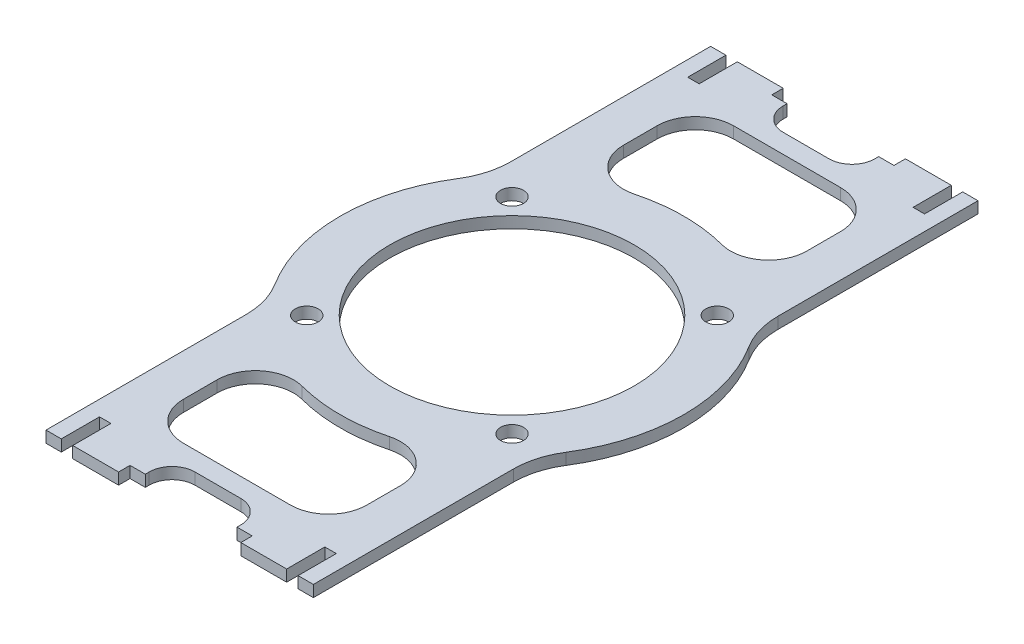
SolidWorks part; units mm, degrees
material "1023 Arkusz stali węglowej (SS)"
ref_plane "Płaszczyzna przednia" through (0, 0, 0) normal (0, 0, 1) x (1, 0, 0)
ref_plane "Płaszczyzna górna" through (0, 0, 0) normal (0, 1, 0) x (1, 0, 0)
ref_plane "Płaszczyzna prawa" through (0, 0, 0) normal (1, 0, 0) x (0, 0, -1)
sketch "Szkic1" plane through (0, 0, 0) normal (0, 1, 0) x (1, 0, 0)
  line L166 (594.7127, -59.8621) -> (606.7127, -59.8621)
  line L167 (606.7127, -59.8621) -> (606.7127, -56.8621)
  line L168 (591.7127, -49.8621) -> (591.7127, -59.8621)
  line L169 (591.7127, -59.8621) -> (587.7127, -59.8621)
  line L170 (610.7127, -56.8621) -> (610.7127, -55.8621)
  line L171 (616.7127, -49.8621) -> (622.7127, -49.8621)
  line L172 (606.7127, -56.8621) -> (610.7127, -56.8621)
  line L173 (587.7127, -59.8621) -> (587.7127, -7.5032)
  line L174 (608.7127, -44.8621) -> (622.7127, -44.8621)
  line L175 (598.7127, -26.0505) -> (598.7127, -34.8621)
  line L176 (594.7127, -59.8621) -> (594.7127, -49.8621)
  line L177 (591.7127, -49.8621) -> (594.7127, -49.8621)
  line L178 (594.7127, 114.1379) -> (606.7127, 114.1379)
  line L179 (606.7127, 114.1379) -> (606.7127, 111.1379)
  line L180 (591.7127, 104.1379) -> (591.7127, 114.1379)
  line L181 (591.7127, 114.1379) -> (587.7127, 114.1379)
  line L182 (610.7127, 111.1379) -> (610.7127, 110.1379)
  line L183 (616.7127, 104.1379) -> (622.7127, 104.1379)
  line L184 (606.7127, 111.1379) -> (610.7127, 111.1379)
  line L185 (587.7127, 114.1379) -> (587.7127, 61.7789)
  line L186 (608.7127, 99.1379) -> (622.7127, 99.1379)
  line L187 (598.7127, 80.3262) -> (598.7127, 89.1379)
  line L188 (594.7127, 114.1379) -> (594.7127, 104.1379)
  line L189 (591.7127, 104.1379) -> (594.7127, 104.1379)
  line L190 (650.7127, -59.8621) -> (638.7127, -59.8621)
  line L191 (638.7127, -59.8621) -> (638.7127, -56.8621)
  line L192 (653.7127, -49.8621) -> (653.7127, -59.8621)
  line L193 (653.7127, -59.8621) -> (657.7127, -59.8621)
  line L194 (634.7127, -56.8621) -> (634.7127, -55.8621)
  line L195 (628.7127, -49.8621) -> (622.7127, -49.8621)
  line L196 (638.7127, -56.8621) -> (634.7127, -56.8621)
  line L197 (657.7127, -59.8621) -> (657.7127, -7.5032)
  line L198 (636.7127, -44.8621) -> (622.7127, -44.8621)
  line L199 (646.7127, -26.0505) -> (646.7127, -34.8621)
  line L200 (650.7127, -59.8621) -> (650.7127, -49.8621)
  line L201 (653.7127, -49.8621) -> (650.7127, -49.8621)
  line L202 (650.7127, 114.1379) -> (638.7127, 114.1379)
  line L203 (638.7127, 114.1379) -> (638.7127, 111.1379)
  line L204 (653.7127, 104.1379) -> (653.7127, 114.1379)
  line L205 (653.7127, 114.1379) -> (657.7127, 114.1379)
  line L206 (634.7127, 111.1379) -> (634.7127, 110.1379)
  line L207 (628.7127, 104.1379) -> (622.7127, 104.1379)
  line L208 (638.7127, 111.1379) -> (634.7127, 111.1379)
  line L209 (657.7127, 114.1379) -> (657.7127, 61.7789)
  line L210 (636.7127, 99.1379) -> (622.7127, 99.1379)
  line L211 (646.7127, 80.3262) -> (646.7127, 89.1379)
  line L212 (650.7127, 114.1379) -> (650.7127, 104.1379)
  line L213 (653.7127, 104.1379) -> (650.7127, 104.1379)
  arc A74 (616.7127, -49.8621) -> (610.7127, -55.8621) centre (616.7127, -55.8621) ccw
  circle A75 centre (622.7127, 27.1379) radius 32
  arc A76 (577.7127, 27.1379) -> (584.6358, 3.1556) centre (622.7127, 27.1379) ccw
  arc A77 (587.7127, -7.5032) -> (584.6358, 3.1556) centre (567.7127, -7.5032) ccw
  circle A78 centre (595.8427, 0.2678) radius 3
  arc A79 (611.2582, -16.3799) -> (622.7127, -17.8621) centre (622.7127, 27.1379) ccw
  arc A80 (598.7127, -34.8621) -> (608.7127, -44.8621) centre (608.7127, -34.8621) ccw
  arc A81 (611.2582, -16.3799) -> (598.7127, -26.0505) centre (608.7127, -26.0505) ccw
  arc A82 (610.7127, 110.1379) -> (616.7127, 104.1379) centre (616.7127, 110.1379) ccw
  circle A83 centre (622.7127, 27.1379) radius 32
  arc A84 (584.6358, 51.1201) -> (577.7127, 27.1379) centre (622.7127, 27.1379) ccw
  arc A85 (584.6358, 51.1201) -> (587.7127, 61.7789) centre (567.7127, 61.7789) ccw
  circle A86 centre (595.8427, 54.0079) radius 3
  arc A87 (622.7127, 72.1379) -> (611.2582, 70.6556) centre (622.7127, 27.1379) ccw
  arc A88 (608.7127, 99.1379) -> (598.7127, 89.1379) centre (608.7127, 89.1379) ccw
  arc A89 (598.7127, 80.3262) -> (611.2582, 70.6556) centre (608.7127, 80.3262) ccw
  arc A90 (634.7127, -55.8621) -> (628.7127, -49.8621) centre (628.7127, -55.8621) ccw
  circle A91 centre (622.7127, 27.1379) radius 32
  arc A92 (660.7897, 3.1556) -> (667.7127, 27.1379) centre (622.7127, 27.1379) ccw
  arc A93 (660.7897, 3.1556) -> (657.7127, -7.5032) centre (677.7127, -7.5032) ccw
  circle A94 centre (649.5828, 0.2678) radius 3
  arc A95 (622.7127, -17.8621) -> (634.1673, -16.3799) centre (622.7127, 27.1379) ccw
  arc A96 (636.7127, -44.8621) -> (646.7127, -34.8621) centre (636.7127, -34.8621) ccw
  arc A97 (646.7127, -26.0505) -> (634.1673, -16.3799) centre (636.7127, -26.0505) ccw
  arc A98 (628.7127, 104.1379) -> (634.7127, 110.1379) centre (628.7127, 110.1379) ccw
  circle A99 centre (622.7127, 27.1379) radius 32
  arc A100 (667.7127, 27.1379) -> (660.7897, 51.1201) centre (622.7127, 27.1379) ccw
  arc A101 (657.7127, 61.7789) -> (660.7897, 51.1201) centre (677.7127, 61.7789) ccw
  circle A102 centre (649.5828, 54.0079) radius 3
  arc A103 (634.1673, 70.6556) -> (622.7127, 72.1379) centre (622.7127, 27.1379) ccw
  arc A104 (646.7127, 89.1379) -> (636.7127, 99.1379) centre (636.7127, 89.1379) ccw
  arc A105 (634.1673, 70.6556) -> (646.7127, 80.3262) centre (636.7127, 80.3262) ccw
extrude "Dodanie-wyciągnięcie1" add sketch "Szkic1" along normal blind 3 contours A101 L209 L205 L204 L213 L212 L202 L203 L208 L206 A98 L207 L183 A82 L182 L184 L179 L178 L188 L189 L180 L181 L185 A85 A84 A76 A77 L173 L169 L168 L177 L176 L166 L167 L172 L170 A74 L171 L195 A90 L194 L196 L191 L190 L200 L201 L192 L193 L197 A93 A92 region at (596.6717, 0, 54.8621)
